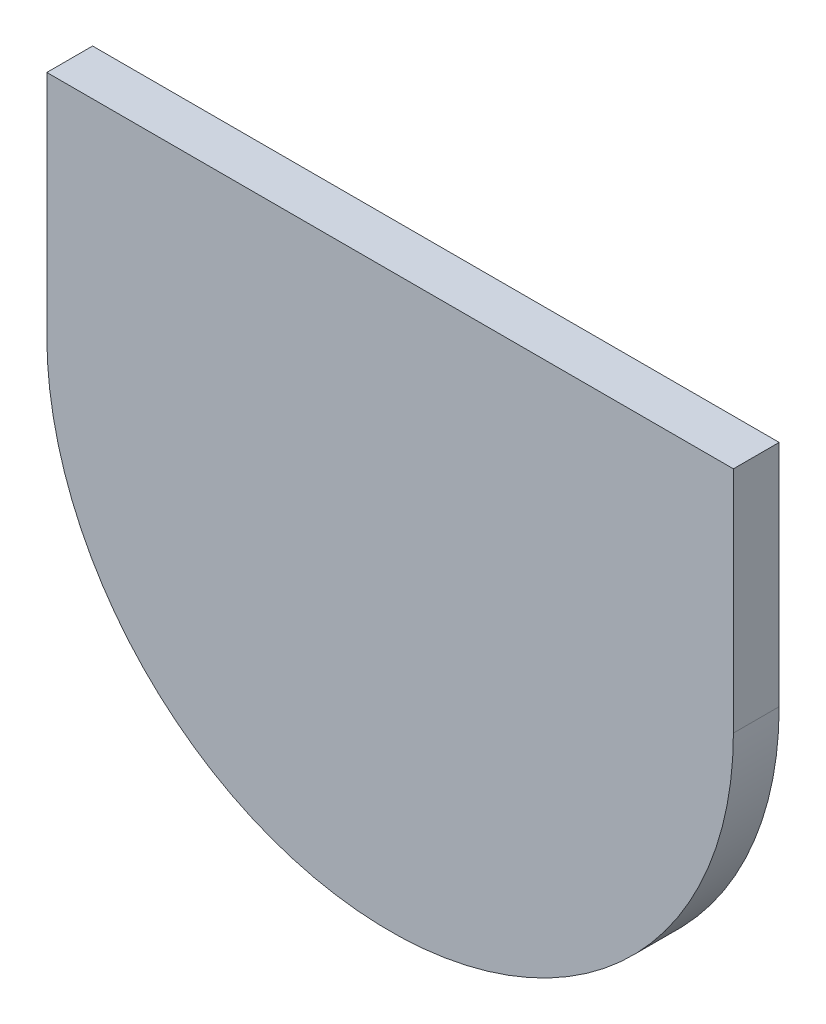
SolidWorks part; units mm, degrees
ref_plane "Front Plane" through (0, 0, 0) normal (0, 0, 1) x (1, 0, 0)
ref_plane "Top Plane" through (0, 0, 0) normal (0, 1, 0) x (1, 0, 0)
ref_plane "Right Plane" through (0, 0, 0) normal (1, 0, 0) x (0, 0, -1)
sketch "Sketch2" plane through (0, 0, 0) normal (0, 0, 1) x (1, 0, 0)
  line L1 (-12.5, 0) -> (-27.5, 0)
  line L2 (-12.5, 0) -> (-12.5, -5)
  line L3 (-12.5, -5) -> (-27.5, -5) construction
  line L4 (-27.5, 0) -> (-27.5, -5)
  arc A0 (-12.5, -5) -> (-27.5, -5) centre (-20, -5) cw
  dimension "D1" = 20
  dimension "D2" = 15
  dimension "D3" = 5
sheet metal parameters "Sheet-Metal1" thickness 1 parameters "D1"=0.7366
base flange "Base-Flange1" sketch "Sketch2" thickness 1 reverse thickness direction no parameters "D1"=0.7366
flat pattern "Flat-Pattern1" [suppressed]
sketch "Bend-Lines1" plane through (0, 0, 0) normal (0, 1, 0) x (1, 0, 0)
sketch3d "Bounding-Box1" [suppressed]
  line L0 (7.5, -7.5, 0) -> (-7.5, -7.5, 0) construction
  line L1 (7.5, 5, 0) -> (-7.5, 5, 0) construction
  line L2 (7.5, -7.5, 0) -> (7.5, 5, 0) construction
  line L3 (-7.5, -7.5, 0) -> (-7.5, 5, 0) construction
